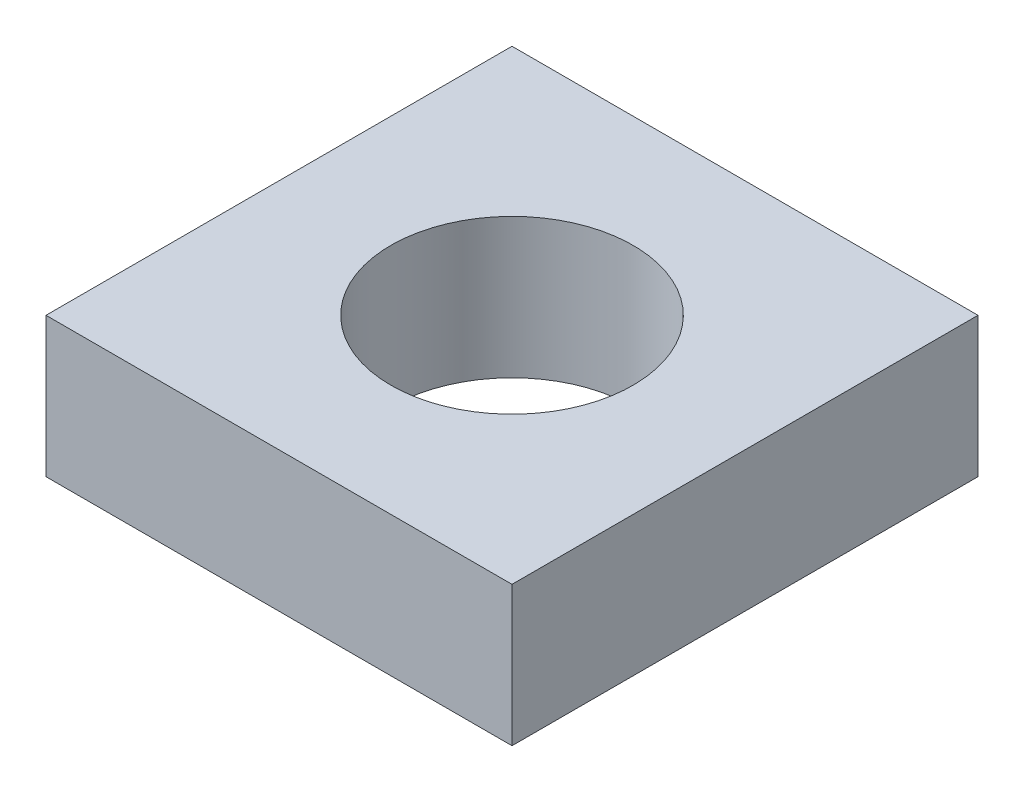
SolidWorks part; units mm, degrees
ref_plane "Front Plane" through (0, 0, 0) normal (0, 0, 1) x (1, 0, 0)
ref_plane "Top Plane" through (0, 0, 0) normal (0, 1, 0) x (1, 0, 0)
ref_plane "Right Plane" through (0, 0, 0) normal (1, 0, 0) x (0, 0, -1)
sketch "Sketch1" plane through (0, 0, 0) normal (0, 1, 0) x (1, 0, 0)
  line L1 (-6.35, 6.35) -> (6.35, 6.35)
  line L2 (-6.35, 6.35) -> (-6.35, -6.35)
  line L3 (-6.35, -6.35) -> (6.35, -6.35)
  line L4 (6.35, 6.35) -> (6.35, -6.35)
  circle A0 centre (0, 0) radius 3.175
  dimension "D1" = 12.7
  dimension "D2" = 12.7
  dimension "D3" = 6.35
  dimension "D4" = 6.35
extrude "Boss-Extrude1" add sketch "Sketch1" along normal blind 3.81 contours L2 L1 L4 L3
sketch "Sketch3" plane through (0, 3.81, 0) normal (0, 1, 0) x (1, 0, 0)
  circle A0 centre (0, 0) radius 3.302
extrude "Cut-Extrude1" cut sketch "Sketch3" against normal through all
